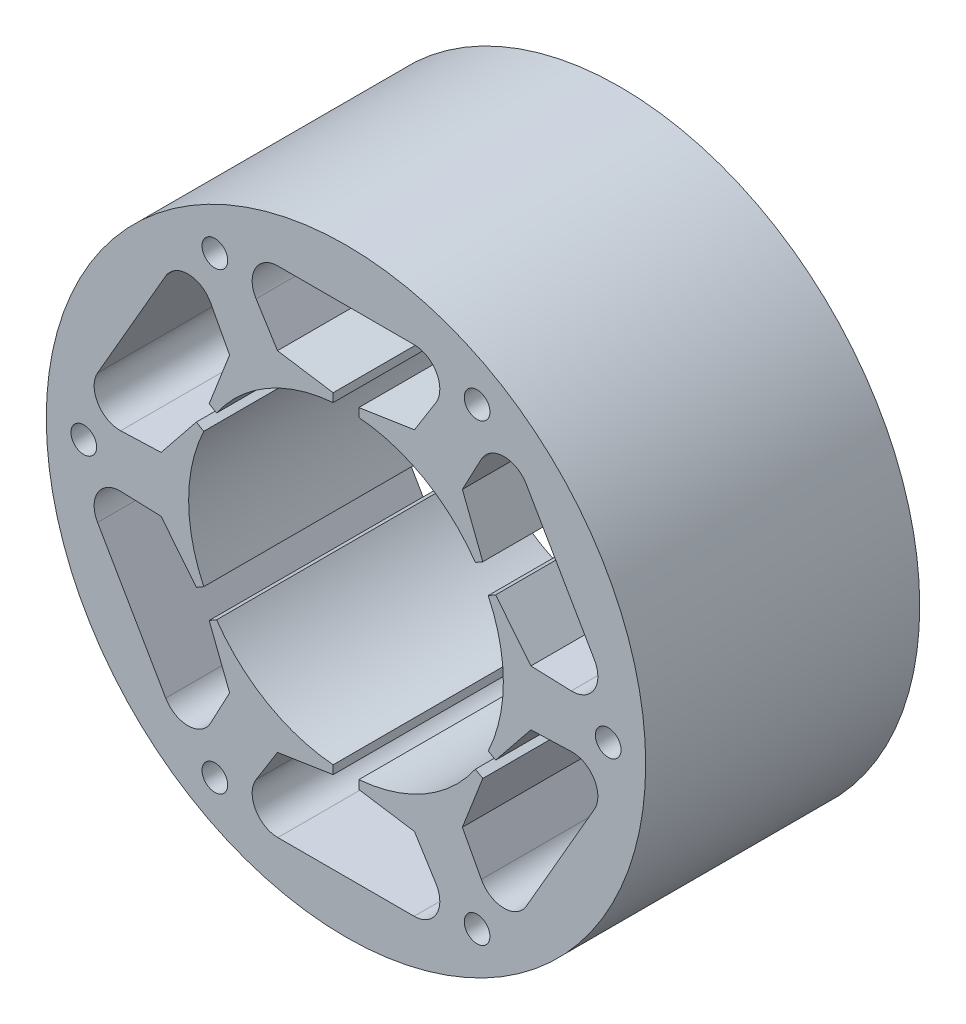
SolidWorks part; units mm, degrees
ref_plane "Ön Düzlem" through (0, 0, 0) normal (0, 0, 1) x (1, 0, 0)
ref_plane "Üst Düzlem" through (0, 0, 0) normal (0, 1, 0) x (1, 0, 0)
ref_plane "Sağ Düzlem" through (0, 0, 0) normal (1, 0, 0) x (0, 0, -1)
sketch "Çizim2" plane through (0, 0, 0) normal (0, 0, 1) x (1, 0, 0)
  line L0 (-15.1101, 10.4559) -> (-15.9761, 10.9559)
  line L1 (-1.5, 19.3137) -> (-1.5, 18.3137)
  line L2 (-8, 20.3137) -> (-1.5, 19.3137)
  line L3 (-10.5, 24.3137) -> (-8, 20.3137)
  line L4 (7.956, 28.9037) -> (-7.956, 28.9037)
  line L5 (8, 20.3137) -> (10.5, 24.3137)
  line L6 (1.5, 19.3137) -> (8, 20.3137)
  line L7 (1.5, 18.3137) -> (1.5, 19.3137)
  line L8 (15.9761, 10.9559) -> (15.1101, 10.4559)
  line L9 (13.5922, 17.085) -> (15.9761, 10.9559)
  line L10 (15.8063, 21.2501) -> (13.5922, 17.085)
  line L11 (29.0093, 7.5617) -> (21.0533, 21.3419)
  line L12 (21.5922, 3.2286) -> (26.3063, 3.0636)
  line L13 (17.4761, 8.3578) -> (21.5922, 3.2286)
  line L14 (16.6101, 7.8578) -> (17.4761, 8.3578)
  line L15 (17.4761, -8.3578) -> (16.6101, -7.8578)
  line L16 (21.5922, -3.2286) -> (17.4761, -8.3578)
  line L17 (26.3063, -3.0636) -> (21.5922, -3.2286)
  line L18 (21.0533, -21.3419) -> (29.0093, -7.5617)
  line L19 (13.5922, -17.085) -> (15.8063, -21.2501)
  line L20 (15.9761, -10.9559) -> (13.5922, -17.085)
  line L21 (15.1101, -10.4559) -> (15.9761, -10.9559)
  line L22 (1.5, -19.3137) -> (1.5, -18.3137)
  line L23 (8, -20.3137) -> (1.5, -19.3137)
  line L24 (10.5, -24.3137) -> (8, -20.3137)
  line L25 (-7.956, -28.9037) -> (7.956, -28.9037)
  line L26 (-8, -20.3137) -> (-10.5, -24.3137)
  line L27 (-1.5, -19.3137) -> (-8, -20.3137)
  line L28 (-1.5, -18.3137) -> (-1.5, -19.3137)
  line L29 (-15.9761, -10.9559) -> (-15.1101, -10.4559)
  line L30 (-13.5922, -17.085) -> (-15.9761, -10.9559)
  line L31 (-15.8063, -21.2501) -> (-13.5922, -17.085)
  line L32 (-29.0093, -7.5617) -> (-21.0533, -21.3419)
  line L33 (-21.5922, -3.2286) -> (-26.3063, -3.0636)
  line L34 (-17.4761, -8.3578) -> (-21.5922, -3.2286)
  line L35 (-16.6101, -7.8578) -> (-17.4761, -8.3578)
  line L36 (-17.4761, 8.3578) -> (-16.6101, 7.8578)
  line L37 (-21.5922, 3.2286) -> (-17.4761, 8.3578)
  line L38 (-26.3063, 3.0636) -> (-21.5922, 3.2286)
  line L39 (-21.0533, 21.3419) -> (-29.0093, 7.5617)
  line L40 (-13.5922, 17.085) -> (-15.8063, 21.2501)
  line L41 (-15.9761, 10.9559) -> (-13.5922, 17.085)
  circle A0 centre (-15.3101, -26.5179) radius 1.5
  circle A1 centre (30.6203, 0) radius 1.5
  circle A2 centre (-15.3101, 26.5179) radius 1.5
  circle A3 centre (0, 0) radius 35
  arc A4 (-1.5, 18.3137) -> (-15.1101, 10.4559) centre (0, 0) ccw
  arc A5 (-7.956, 28.9037) -> (-10.5, 24.3137) centre (-7.956, 25.9037) ccw
  arc A6 (10.5, 24.3137) -> (7.956, 28.9037) centre (7.956, 25.9037) ccw
  arc A7 (15.1101, 10.4559) -> (1.5, 18.3137) centre (0, 0) ccw
  arc A8 (21.0533, 21.3419) -> (15.8063, 21.2501) centre (18.4552, 19.8419) ccw
  arc A9 (26.3063, 3.0636) -> (29.0093, 7.5617) centre (26.4112, 6.0617) ccw
  arc A10 (16.6101, -7.8578) -> (16.6101, 7.8578) centre (0, 0) ccw
  arc A11 (29.0093, -7.5617) -> (26.3063, -3.0636) centre (26.4112, -6.0617) ccw
  arc A12 (15.8063, -21.2501) -> (21.0533, -21.3419) centre (18.4552, -19.8419) ccw
  arc A13 (1.5, -18.3137) -> (15.1101, -10.4559) centre (0, 0) ccw
  arc A14 (7.956, -28.9037) -> (10.5, -24.3137) centre (7.956, -25.9037) ccw
  arc A15 (-10.5, -24.3137) -> (-7.956, -28.9037) centre (-7.956, -25.9037) ccw
  arc A16 (-15.1101, -10.4559) -> (-1.5, -18.3137) centre (0, 0) ccw
  arc A17 (-21.0533, -21.3419) -> (-15.8063, -21.2501) centre (-18.4552, -19.8419) ccw
  arc A18 (-26.3063, -3.0636) -> (-29.0093, -7.5617) centre (-26.4112, -6.0617) ccw
  arc A19 (-16.6101, 7.8578) -> (-16.6101, -7.8578) centre (0, 0) ccw
  arc A20 (-29.0093, 7.5617) -> (-26.3063, 3.0636) centre (-26.4112, 6.0617) ccw
  arc A21 (-15.8063, 21.2501) -> (-21.0533, 21.3419) centre (-18.4552, 19.8419) ccw
  circle A22 centre (15.3101, 26.5179) radius 1.5
  circle A23 centre (15.3101, -26.5179) radius 1.5
  circle A24 centre (-30.6203, 0) radius 1.5
extrude "Yükseklik-Ekstrüzyon1" add sketch "Çizim2" along normal blind 32
